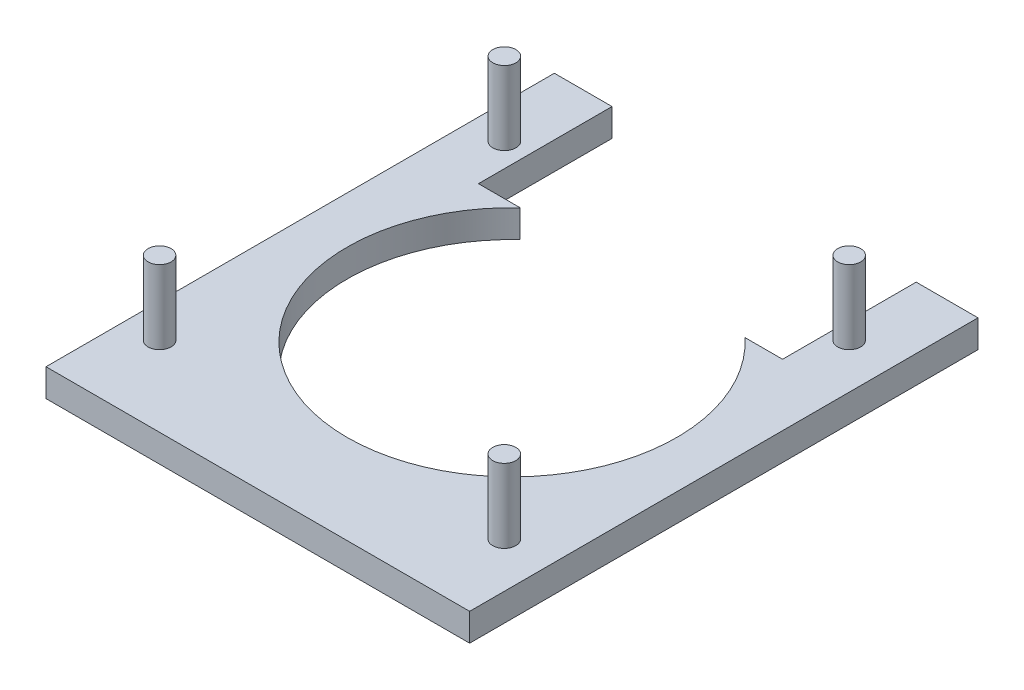
SolidWorks part; units mm, degrees
ref_plane "Front Plane" through (0, 0, 0) normal (0, 0, 1) x (1, 0, 0)
ref_plane "Top Plane" through (0, 0, 0) normal (0, 1, 0) x (1, 0, 0)
ref_plane "Right Plane" through (0, 0, 0) normal (1, 0, 0) x (0, 0, -1)
sketch "Sketch1" plane through (0, 0, 0) normal (0, 1, 0) x (1, 0, 0)
  line L1 (-23, -27.6) -> (23, -27.6)
  line L2 (-23, -27.6) -> (-23, 27.6)
  line L3 (-23, 27.6) -> (23, 27.6)
  line L4 (23, -27.6) -> (23, 27.6)
  line L5 (-23, -27.6) -> (23, 27.6) construction
  line L6 (-23, 27.6) -> (23, -27.6) construction
  point P0 (0, 0)
extrude "Boss-Extrude1" add sketch "Sketch1" along normal blind 3
sketch "Sketch2" plane through (0, 3, 0) normal (0, 1, 0) x (1, 0, 0)
  line L0 (-19.3179, 18.49) -> (18.1221, 18.49)
  line L1 (-19.3179, 18.49) -> (-19.3179, -18.95)
  line L2 (-19.3179, -18.95) -> (18.1221, -18.95)
  line L3 (18.1221, 18.49) -> (18.1221, -18.95)
  circle A0 centre (-19.3179, 18.49) radius 1.25
  circle A1 centre (18.1221, 18.49) radius 1.25
  circle A2 centre (-19.3179, -18.95) radius 1.25
  circle A3 centre (18.1221, -18.95) radius 1.25
sketch "Sketch3" plane through (0, 3, 0) normal (0, 1, 0) x (1, 0, 0)
  circle A0 centre (0, 0) radius 17.9
sketch "Sketch4" plane through (0, 3, 0) normal (0, 1, 0) x (1, 0, 0)
  line L1 (-16.7358, 33.9203) -> (16.2875, 33.9203)
  line L2 (-16.7358, 33.9203) -> (-16.7358, 13.0921)
  line L3 (-16.7358, 13.0921) -> (16.2875, 13.0921)
  line L4 (16.2875, 33.9203) -> (16.2875, 13.0921)
  line L5 (-16.7358, 33.9203) -> (16.2875, 13.0921) construction
  line L6 (-16.7358, 13.0921) -> (16.2875, 33.9203) construction
  point P0 (-0.2241, 23.5062)
extrude "Cut-Extrude1" cut sketch "Sketch4" against normal blind 8 contours L2 L1 L4 L3
sketch "Sketch5" plane through (0, 3, 0) normal (0, 1, 0) x (1, 0, 0)
  circle A0 centre (-19.3179, 18.49) radius 1.25
  circle A1 centre (18.1221, 18.49) radius 1.25
  circle A2 centre (-19.3179, -18.95) radius 1.25
  circle A3 centre (18.0841, -18.9245) radius 1.25
  point P8 (18.1221, 18.49)
  point P9 (-19.3179, -18.95)
  point P10 (-19.3179, 18.49)
  point P14 (-19.3179, 18.49)
extrude "Cut-Extrude2" cut sketch "Sketch3" against normal blind 8
extrude "Boss-Extrude2" add sketch "Sketch5" along normal blind 8
